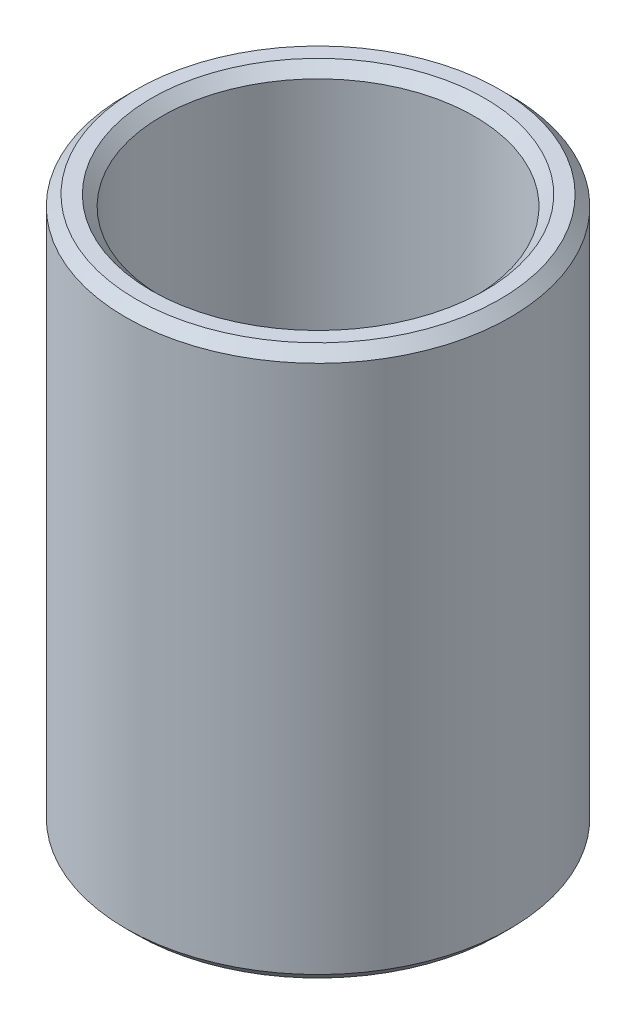
SolidWorks part; units mm, degrees
ref_plane "Front Plane" through (0, 0, 0) normal (0, 0, 1) x (1, 0, 0)
ref_plane "Top Plane" through (0, 0, 0) normal (0, 1, 0) x (1, 0, 0)
ref_plane "Right Plane" through (0, 0, 0) normal (1, 0, 0) x (0, 0, -1)
sketch "Sketch1" plane through (0, 0, 0) normal (0, 1, 0) x (1, 0, 0)
  circle A0 centre (0, 0) radius 15
  dimension "SLEEVE_OD" = 30
extrude "Boss-Extrude1" add sketch "Sketch1" along normal blind 42.9359
sketch "Sketch2" plane through (0, 0, 0) normal (0, 1, 0) x (1, 0, 0)
  circle A0 centre (0, 0) radius 12.1961
  dimension "BORE_D" = 24.3921
extrude "Cut-Extrude1" cut sketch "Sketch2" along normal through all
chamfer "Chamfer1" distance 0.8125 angle 45 4 edges at (0, 42.9359, 12.1961) (0, 0, 12.1961) (0, 0, 15) (0, 42.9359, 15)
